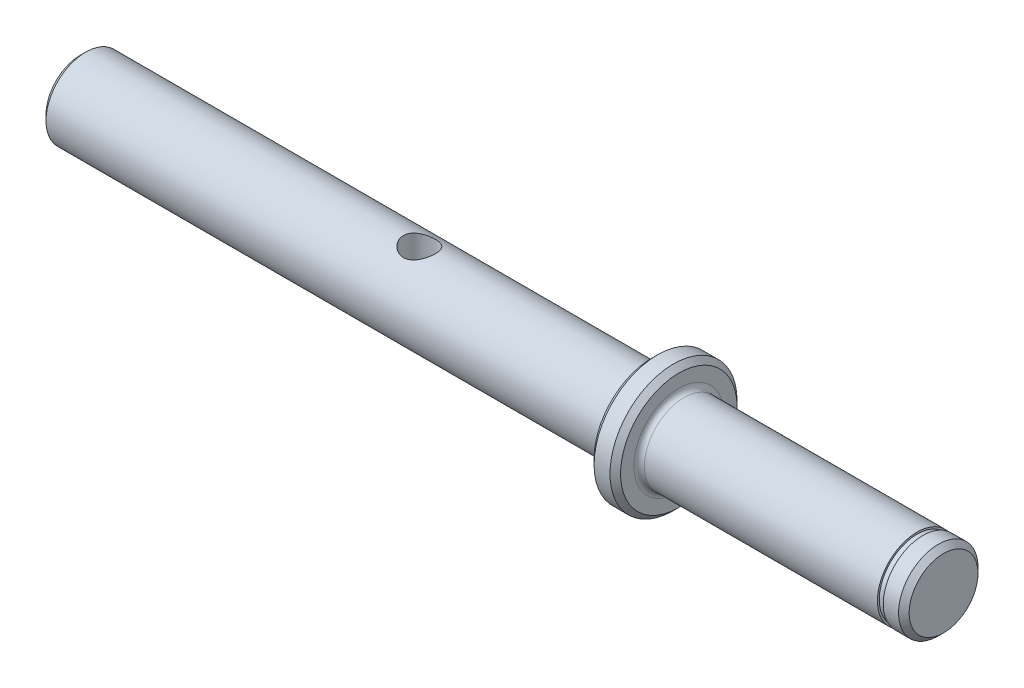
SolidWorks part; units mm, degrees
ref_plane "Front Plane" through (0, 0, 0) normal (0, 0, 1) x (1, 0, 0)
ref_plane "Top Plane" through (0, 0, 0) normal (0, 1, 0) x (1, 0, 0)
ref_plane "Right Plane" through (0, 0, 0) normal (1, 0, 0) x (0, 0, -1)
ref_axis "X" through (-88.99, 0, 0) along (1, 0, 0)
ref_axis "Y" through (0, 0, -88.99) along (0, 0, 1)
ref_axis "Z" through (0, 55, 0) along (0, -1, 0)
sketch "Sketch1" plane through (0, 0, 0) normal (0, 0, 1) x (1, 0, 0)
  line L0 (0, 0) -> (-28.2258, 0) construction
  line L1 (0, 0) -> (0, 7.5)
  line L2 (0, 7.5) -> (108, 7.5)
  line L3 (163, 7.5) -> (163, 0)
  line L4 (163, 0) -> (0, 0)
  line L15 (113, 7.5) -> (158, 7.5)
  line L22 (159.1, 7.5) -> (163, 7.5)
  line L24 (108, 7.5) -> (108, 12)
  line L25 (108, 12) -> (113, 12)
  line L26 (113, 7.5) -> (113, 12)
  line L28 (158, 7.5) -> (158, 7.15)
  line L29 (158, 7.15) -> (159.1, 7.15)
  line L30 (159.1, 7.5) -> (159.1, 7.15)
  dimension "D1" = 15
  dimension "D2" = 163
  dimension "D3" = 50
  dimension "D4" = 5
  dimension "D5" = 12
  dimension "D6" = 45
  dimension "D7" = 7.15
  dimension "D8" = 1.1
revolve "Revolve1" add sketch "Sketch1" angle 360 about L0
ref_plane "Plane1" through (81.5, 0, 0) normal (1, 0, 0) x (0, 0, -1)
sketch "Sketch2" plane through (0, 0, 0) normal (0, 1, 0) x (1, 0, 0)
  line L1 (81.5, -7.15) -> (81.5, 7.15) construction
  circle A0 centre (64, 0) radius 3
  dimension "D1" = 6
  dimension "D2" = 17.5
extrude "Cut-Extrude1" cut sketch "Sketch2" against normal blind 10 and the other way blind 10
chamfer "Chamfer1" distance 1 angle 45 4 edges at (113, 0, -12) (108, 0, -12) (0, 0, -7.5) (163, 0, -7.5)
fillet "Fillet1" radius 2 1 edges at (108, 0, -7.5)
fillet "Fillet2" radius 1 1 edges at (113, 0, -7.5)
